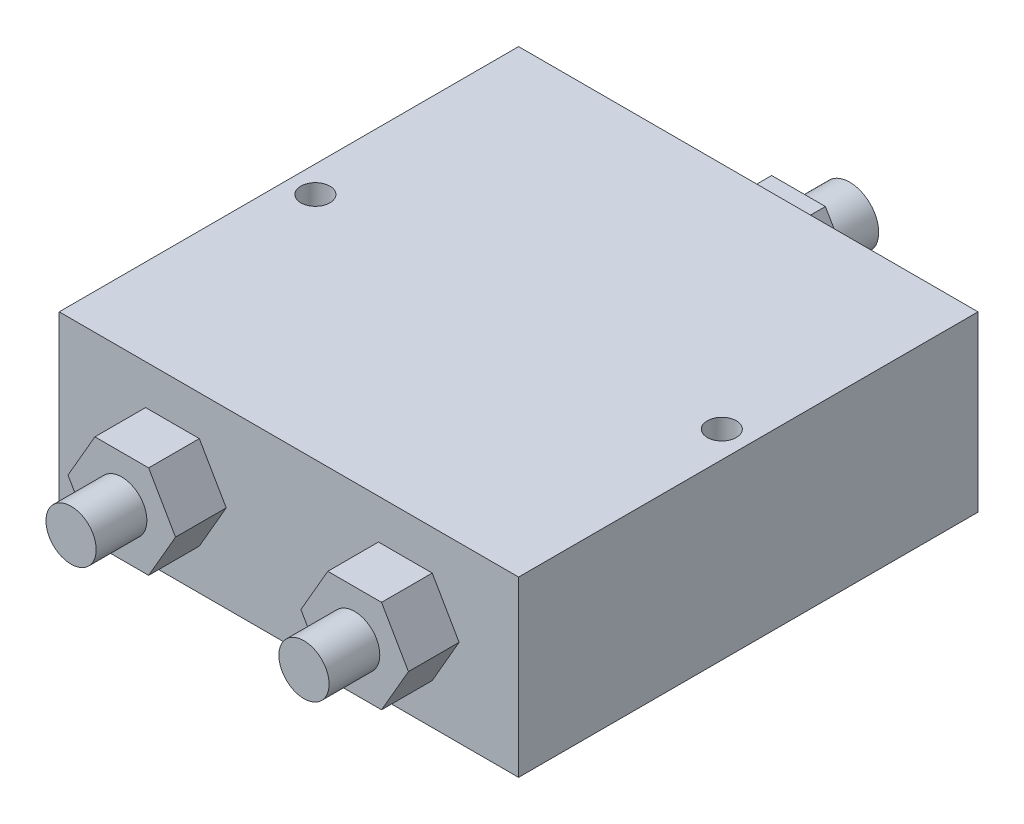
SolidWorks part; units mm, degrees
ref_plane "Front Plane" through (0, 0, 0) normal (0, 0, 1) x (1, 0, 0)
ref_plane "Top Plane" through (0, 0, 0) normal (0, 1, 0) x (1, 0, 0)
ref_plane "Right Plane" through (0, 0, 0) normal (1, 0, 0) x (0, 0, -1)
sketch "Sketch1" plane through (0, 0, 0) normal (0, 1, 0) x (1, 0, 0)
  line L1 (25.15, -25.15) -> (-25.15, -25.15)
  line L2 (25.15, -25.15) -> (25.15, 25.15)
  line L3 (25.15, 25.15) -> (-25.15, 25.15)
  line L4 (-25.15, -25.15) -> (-25.15, 25.15)
  line L5 (25.15, -25.15) -> (-25.15, 25.15) construction
  line L6 (25.15, 25.15) -> (-25.15, -25.15) construction
  point P0 (0, 0)
  dimension "D1" = 50.3
  dimension "D2" = 50.3
extrude "Boss-Extrude1" add sketch "Sketch1" along normal blind 19
sketch "Sketch2" plane through (0, 0, 25.15) normal (0, 0, 1) x (1, 0, 0)
  line L0 (-25.15, 19) -> (-25.15, 0) construction
  line L1 (-15.6929, 4.4546) -> (-9.8071, 4.4546)
  line L2 (-9.8071, 4.4546) -> (-6.8642, 9.5518)
  line L3 (-6.8642, 9.5518) -> (-9.8071, 14.649)
  line L4 (-9.8071, 14.649) -> (-15.6929, 14.649)
  line L5 (-15.6929, 14.649) -> (-18.6358, 9.5518)
  line L6 (-18.6358, 9.5518) -> (-15.6929, 4.4546)
  line L7 (0, 19) -> (0, 0)
  line L8 (-25.15, 19) -> (25.15, 19) construction
  line L9 (-25.15, 0) -> (25.15, 0) construction
  line L10 (15.6929, 4.4546) -> (9.8071, 4.4546)
  line L11 (9.8071, 4.4546) -> (6.8642, 9.5518)
  line L12 (6.8642, 9.5518) -> (9.8071, 14.649)
  line L13 (9.8071, 14.649) -> (15.6929, 14.649)
  line L14 (15.6929, 14.649) -> (18.6358, 9.5518)
  line L15 (18.6358, 9.5518) -> (15.6929, 4.4546)
  circle A0 centre (-12.75, 9.5518) radius 5.0972 construction
  circle A1 centre (12.75, 9.5518) radius 5.0972 construction
  dimension "D1" = 12.4
extrude "Boss-Extrude2" add sketch "Sketch2" along normal blind 5.55 contours L5 L6 L1 L2 L3 L4 | L15 L14 L13 L12 L11 L10 region at (-12.75, 9.5518, 25.15) region at (12.75, 9.5518, 25.15)
sketch "Sketch4" plane through (0, 0, -25.15) normal (0, 0, -1) x (-1, 0, 0)
  line L1 (-5.8355, 9.9844) -> (-2.8928, 4.8874)
  line L2 (-2.8928, 4.8874) -> (2.9928, 4.8874)
  line L3 (2.9928, 4.8874) -> (5.9355, 9.9844)
  line L4 (5.9355, 9.9844) -> (2.9928, 15.0814)
  line L5 (2.9928, 15.0814) -> (-2.8928, 15.0814)
  line L6 (-2.8928, 15.0814) -> (-5.8355, 9.9844)
  line L8 (25.15, 19) -> (25.15, 0) construction
  circle A0 centre (0.05, 9.9844) radius 5.097 construction
  dimension "D1" = 25.1
extrude "Boss-Extrude3" add sketch "Sketch4" along normal blind 5.55
sketch "Sketch5" plane through (0, 0, -30.7) normal (0, 0, -1) x (-1, 0, 0)
  line L1 (2.9928, 15.0814) -> (-2.8928, 15.0814) construction
  circle A0 centre (0, 9.9964) radius 3.175
  point P4 (0.05, 15.0814)
  dimension "D1" = 5.085
extrude "Boss-Extrude4" add sketch "Sketch5" along normal blind 5.55
sketch "Sketch7" plane through (0, 0, 30.7) normal (0, 0, 1) x (1, 0, 0)
  line L0 (-9.8071, 14.649) -> (-15.6929, 14.649) construction
  line L1 (0, 0) -> (0, 19.0446)
  circle A0 centre (-12.7508, 9.564) radius 2.75
  circle A1 centre (12.7508, 9.564) radius 2.75
  point P2 (-12.75, 14.649)
  dimension "D1" = 5.085
  dimension "D3" = 5.5
  dimension "D2" = 5.885
extrude "Boss-Extrude5" add sketch "Sketch7" along normal blind 5.55 contours A0 | A1 region at (-12.7508, 9.564, 30.7) region at (12.7508, 9.564, 30.7)
sketch "Sketch8" plane through (0, 19, 0) normal (0, 1, 0) x (1, 0, 0)
  line L0 (-25.15, 25.15) -> (-25.15, -25.15) construction
  line L1 (0, 25.15) -> (0, -25.15)
  line L2 (25.15, 25.15) -> (-25.15, 25.15) construction
  line L3 (-25.15, -25.15) -> (25.15, -25.15) construction
  circle A0 centre (-22.25, 0) radius 1.59
  circle A1 centre (22.25, 0) radius 1.59
  dimension "D1" = 2.9
extrude "Cut-Extrude1" cut sketch "Sketch8" against normal through all contours A0 | A1
